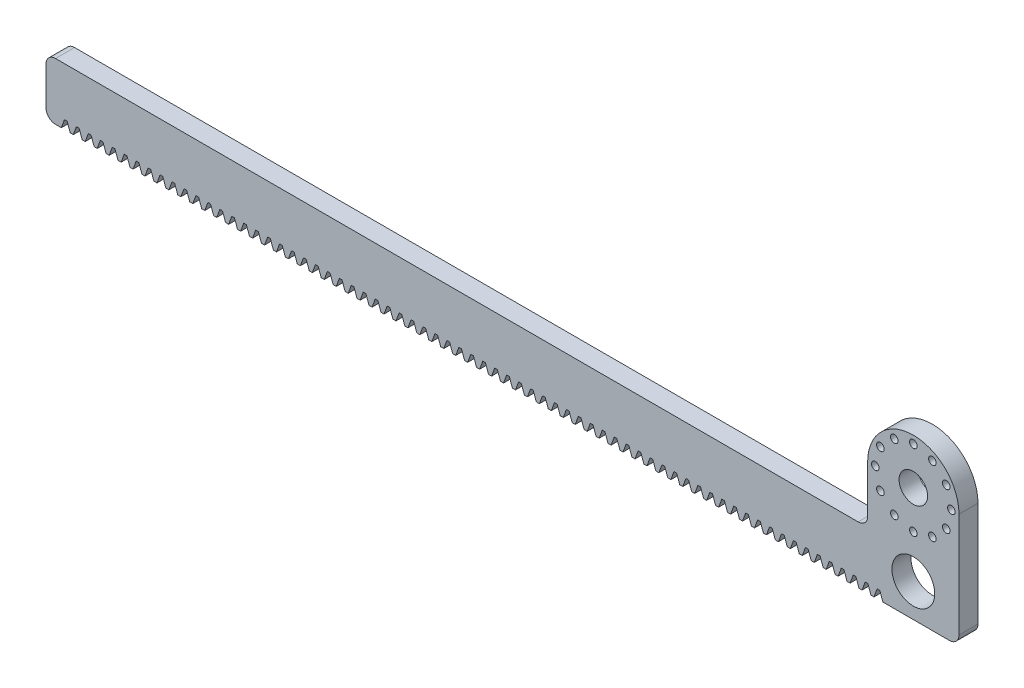
SolidWorks part; units mm, degrees
material "PC High Viscosity"
ref_plane "Front Plane" through (0, 0, 0) normal (0, 0, 1) x (1, 0, 0)
ref_plane "Top Plane" through (0, 0, 0) normal (0, 1, 0) x (1, 0, 0)
ref_plane "Right Plane" through (0, 0, 0) normal (1, 0, 0) x (0, 0, -1)
sketch "Sketch1" plane through (0, 0, 0) normal (0, 0, 1) x (1, 0, 0)
  line L2 (0, 0) -> (0, 38.1)
  line L3 (0, 38.1) -> (40.5308, 38.1)
  line L8 (40.5308, 38.1) -> (548.64, 38.1)
  line L9 (0, 0) -> (609.6, 0)
  line L19 (590.55, 0) -> (590.55, 10.0162) construction
  line L20 (590.55, 10.0162) -> (76.2, 10.0162) construction
  line L21 (76.2, 10.0162) -> (76.2, 0) construction
  line L22 (609.6, 76.2) -> (609.6, 0)
  line L27 (548.64, 76.2) -> (548.64, 38.1)
  line L28 (560.3214, 25.4803) -> (569.7207, 77.8858) construction
  line L29 (588.5193, 77.8858) -> (597.9186, 25.4803) construction
  circle A1 centre (579.12, 76.2) radius 9.525
  circle A2 centre (579.12, 76.2) radius 25.4 construction
  circle A3 centre (579.12, 101.6) radius 2.54
  circle A4 centre (591.82, 98.197) radius 2.54
  circle A5 centre (601.117, 88.9) radius 2.54
  circle A6 centre (604.52, 76.2) radius 2.54
  circle A7 centre (601.117, 63.5) radius 2.54
  circle A8 centre (591.82, 54.203) radius 2.54
  circle A9 centre (579.12, 50.8) radius 2.54
  circle A10 centre (566.42, 54.203) radius 2.54
  circle A11 centre (557.123, 63.5) radius 2.54
  circle A12 centre (553.72, 76.2) radius 2.54
  circle A13 centre (557.123, 88.9) radius 2.54
  circle A14 centre (566.42, 98.197) radius 2.54
  arc A15 (609.6, 76.2) -> (548.64, 76.2) centre (579.12, 76.2) ccw
  circle A16 centre (557.123, 88.9) radius 5.08 construction
  arc A17 (588.5193, 77.8858) -> (569.7207, 77.8858) centre (579.12, 76.2) ccw construction
  arc A18 (560.3214, 25.4803) -> (597.9186, 25.4803) centre (579.12, 22.1086) ccw construction
  circle A19 centre (579.12, 22.1086) radius 14.2875
  point P48 (579.12, 76.2)
  dimension "D3" = 5.08
  dimension "D4" = 50.8
  dimension "D9" = 10.16
  dimension "D5" = 19.05
  dimension "D12" = 28.575
  dimension "D2" = 38.1
  dimension "D1" = 609.6
  dimension "D7" = 76.2
  dimension "D8" = 38.1
  dimension "D6" = 12
extrude "Boss-Extrude1" add sketch "Sketch1" along normal blind 12.7 contours L3 | L3 L2 region at (332.535, 25.1889, 0)
fillet "Fillet2" radius 6.35 4 edges at (0, 38.1, 6.35) (0, 0, 6.35) (548.64, 38.1, 6.35) (609.6, 0, 6.35)
sketch "Sketch2" plane through (0, 0, 12.7) normal (0, 0, 1) x (1, 0, 0)
  line L0 (558.8, 0) -> (43.7057, 0)
  line L1 (43.7057, 0) -> (43.7057, 5.715)
  line L2 (43.7057, 5.715) -> (558.8, 5.715)
  line L3 (558.8, 5.715) -> (558.8, 0)
  line L5 (557.8755, 2.54) -> (549.711, 2.54) construction
  line L6 (558.8, 0) -> (556.7199, 5.715)
  line L7 (609.6, 76.2) -> (609.6, 6.35) construction
  line L8 (552.8688, 0) -> (558.8, 0)
  line L10 (556.7199, 5.715) -> (554.9488, 5.715)
  line L11 (558.8, 0) -> (552.8688, 0)
  line L12 (552.8688, 0) -> (554.9488, 5.715)
  line L13 (554.9488, 5.715) -> (556.7199, 5.715)
  line L14 (558.8, 0) -> (552.8688, 0)
  line L15 (554.9488, 5.715) -> (556.7199, 5.715)
  line L16 (558.8, 0) -> (552.8688, 0)
  line L17 (552.8688, 0) -> (558.8, 0)
  line L19 (556.7199, 5.715) -> (554.9488, 5.715) construction
  line L20 (552.8688, 0) -> (558.8, 0) construction
  line L23 (0, 0) -> (609.6, 0) construction
  point P8 (553.7932, 2.54)
  point P16 (557.8755, 2.54)
  dimension "D1" = 70
  dimension "D2" = 2.54
  dimension "D3" = 3.175
  dimension "D4" = 70
  dimension "D5" = 1.7711
  dimension "D6" = 50.8
  dimension "D7" = 515.0943
extrude "Cut-Extrude1" cut sketch "Sketch2" against normal through all contours L12 L0 L8 L6 L2 region at (555.8344, 2.343, 12.7)
pattern_linear "LPattern1" count 69 spacing 7.9796 along (-1, 0, 0) of "Cut-Extrude1"
equation "\"D11@Sketch1\"=(24*5mm)/pi"
equation "\"D10@Sketch1\"=(12*5mm)/pi"
equation "\"D13@Sketch1\"=(40*5mm)-0.005"
